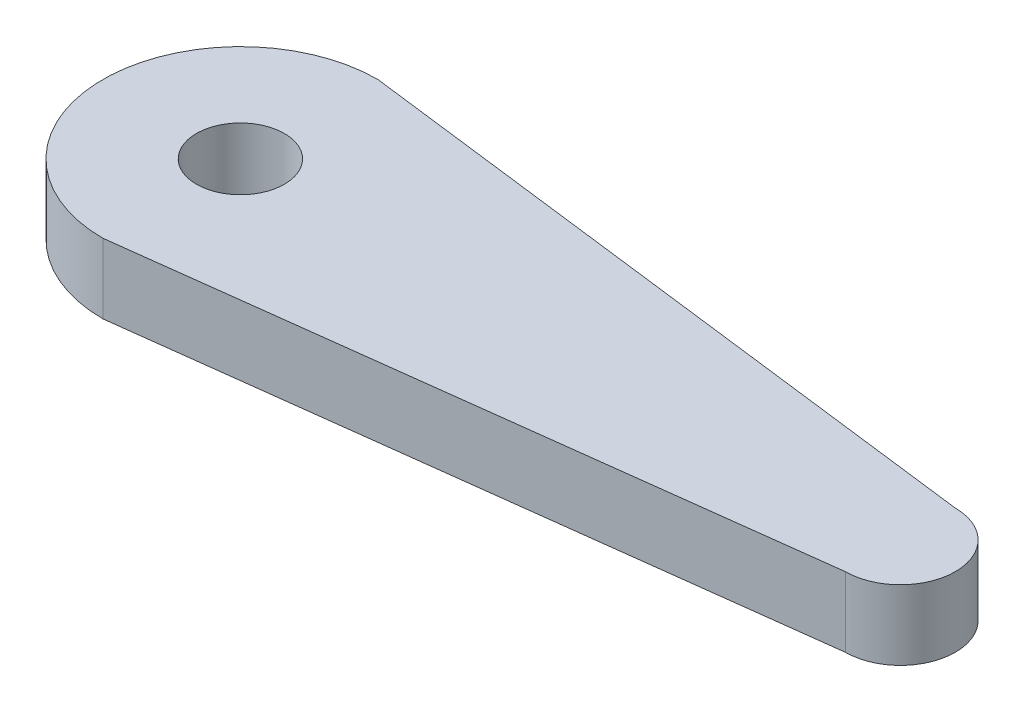
SolidWorks part; units mm, degrees
ref_plane "Front Plane" through (0, 0, 0) normal (0, 0, 1) x (1, 0, 0)
ref_plane "Top Plane" through (0, 0, 0) normal (0, 1, 0) x (1, 0, 0)
ref_plane "Right Plane" through (0, 0, 0) normal (1, 0, 0) x (0, 0, -1)
sketch "Sketch1" plane through (0, 0, 0) normal (0, 1, 0) x (1, 0, 0)
  line L0 (0, 0) -> (60, 0) construction
  line L1 (0, -12.5) -> (0, 12.5) construction
  line L2 (60, -5) -> (60, 5) construction
  line L3 (0, 12.5) -> (60, 5)
  line L4 (60, -5) -> (0, -12.5)
  arc A0 (3.0769, 12.1154) -> (3.0769, -12.1154) centre (0, 0) ccw
  arc A1 (60, -5) -> (60, 5) centre (60, 0) ccw
  circle A2 centre (0, 0) radius 4
  dimension "D1" = 25
  dimension "D2" = 10
  dimension "D4" = 8
  dimension "D3" = 60
extrude "Boss-Extrude1" add sketch "Sketch1" along normal blind 6.35 contours L4 A1 L3 A0 A2 region at (21.9064, 0, 0)
